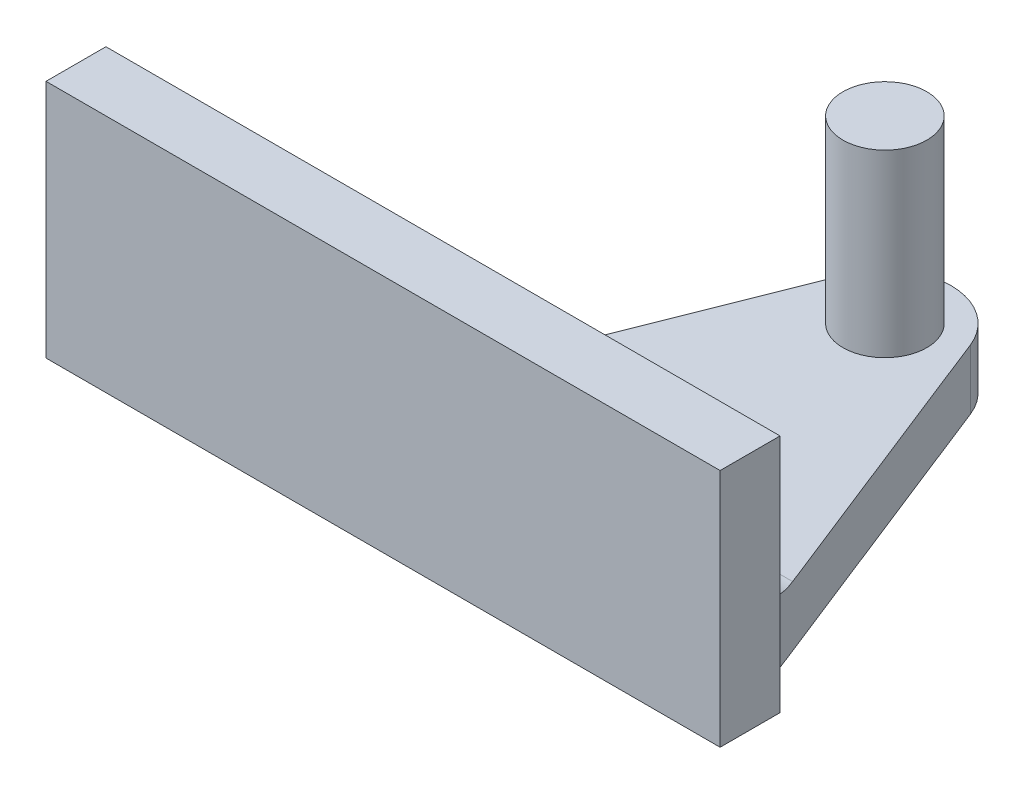
SolidWorks part; units mm, degrees
ref_plane "Front Plane" through (0, 0, 0) normal (0, 0, 1) x (1, 0, 0)
ref_plane "Top Plane" through (0, 0, 0) normal (0, 1, 0) x (1, 0, 0)
ref_plane "Right Plane" through (0, 0, 0) normal (1, 0, 0) x (0, 0, -1)
sketch "Sketch1" plane through (0, 0, 0) normal (0, 1, 0) x (1, 0, 0)
  line L0 (-10.2309, 4.0409) -> (-37.5, -65)
  line L1 (-37.5, -65) -> (37.5, -65)
  line L2 (37.5, -65) -> (10.2309, 4.0409)
  line L8 (-75, -65) -> (37.5, -65)
  line L9 (-75, -65) -> (-75, -55)
  line L10 (-75, -55) -> (37.5, -55)
  line L11 (37.5, -65) -> (37.5, -55)
  circle A0 centre (0, 0) radius 7
  circle A1 centre (0, 0) radius 11
  point P7 (0, -65)
  dimension "D1" = 14
  dimension "D3" = 65
  dimension "D4" = 75
  dimension "D5" = 10
  dimension "D6" = 75
  dimension "D2" = 4
extrude "Boss-Extrude1" add sketch "Sketch1" along normal blind 10 contours L10 L9 L8 L0 | L10 L0 L1 L2 | L2 L11 L10 | A1 L0 L10 L2 | A1 A0 | A0 region at (0, 0, 34.0975) region at (0, 0, -10.6889) region at (0, 0, 60.0927) region at (-55.2461, 0, 59.9166) region at (36.1834, 0, 58.3333) region at (0, 0, 0)
extrude "Boss-Extrude2" add sketch "Sketch1<3>" along normal blind 30 from surface contours A0 | L8 L9 L10 L11 region at (0, 0, 0) starting at face at (-9.375, 10, 41.8699)
sketch "Sketch1<3>" plane through (0, 0, 0) normal (0, 1, 0) x (1, 0, 0) same geometry as "Sketch1"
fillet "Fillet1" radius 10 3 edges at (33.5503, 5, 55) (-33.5503, 5, 55) (0, 10, 55)
